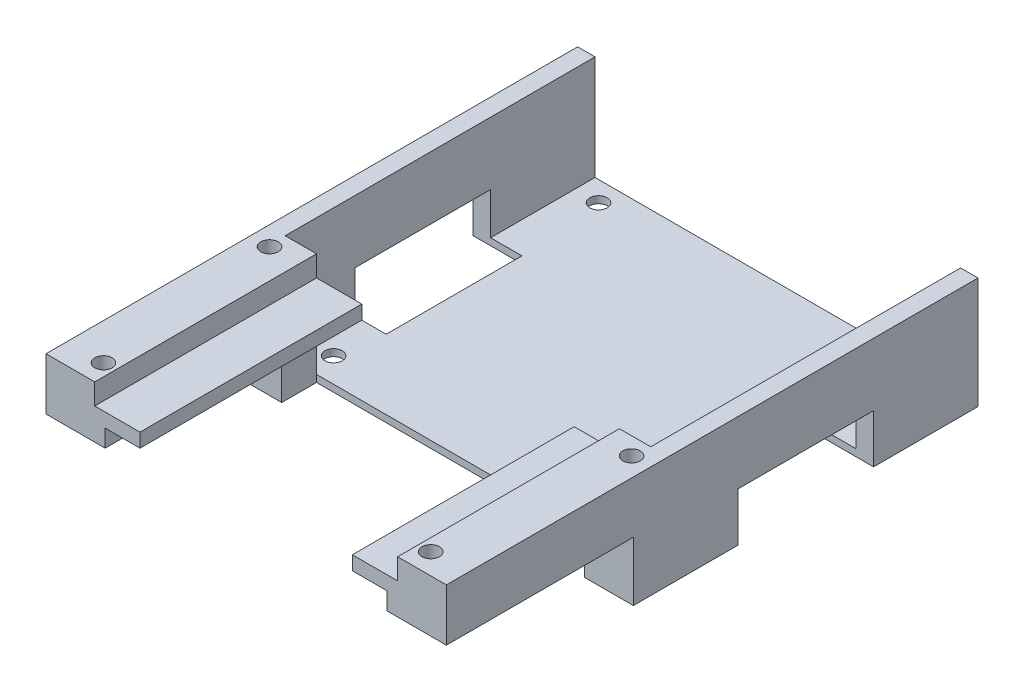
SolidWorks part; units mm, degrees
ref_plane "Front Plane" through (0, 0, 0) normal (0, 0, 1) x (1, 0, 0)
ref_plane "Top Plane" through (0, 0, 0) normal (0, 1, 0) x (1, 0, 0)
ref_plane "Right Plane" through (0, 0, 0) normal (1, 0, 0) x (0, 0, -1)
sketch "Sketch1" plane through (0, 0, 0) normal (0, 1, 0) x (1, 0, 0)
  line L0 (0, 0) -> (0, 76.35) construction
  line L1 (-28.75, 76.35) -> (28.75, 76.35)
  line L2 (28.75, 76.35) -> (28.75, 0)
  line L3 (28.75, 0) -> (21.75, 0)
  line L4 (21.75, 0) -> (21.75, 31.85)
  line L5 (21.75, 31.85) -> (-21.75, 31.85)
  line L6 (-21.75, 31.85) -> (-21.75, 0)
  line L7 (-21.75, 0) -> (-28.75, 0)
  line L8 (-28.75, 0) -> (-28.75, 76.35)
  line L9 (-26.25, 76.35) -> (-26.25, 31.85)
  line L14 (-26.25, 31.85) -> (-21.75, 31.85)
  line L15 (26.25, 76.35) -> (26.25, 31.85)
  line L16 (26.25, 31.85) -> (21.75, 31.85)
  line L17 (28.75, 74.35) -> (30.25, 74.35)
  line L18 (-28.75, 41.35) -> (-26.25, 41.35)
  line L19 (-28.75, 41.35) -> (-28.75, 53.35)
  line L20 (-28.75, 53.35) -> (-26.25, 53.35)
  line L21 (-26.25, 41.35) -> (-26.25, 53.35)
  line L22 (30.25, 68.35) -> (28.75, 68.35)
  line L23 (-30.25, 68.35) -> (-28.75, 68.35)
  line L24 (-28.75, 74.35) -> (-30.25, 74.35)
  arc A0 (30.25, 68.35) -> (30.25, 74.35) centre (30.25, 71.35) ccw
  arc A1 (-30.25, 68.35) -> (-30.25, 74.35) centre (-30.25, 71.35) cw
  point P10 (0, 76.35)
  point P16 (-27.5, 41.35)
  point P17 (-22.85, 73.45)
  point P18 (22.85, 73.45)
  point P23 (22.85, 35.4)
  point P24 (-22.85, 35.4)
  point P25 (23.5, 3)
  point P26 (26, 29.35)
  point P27 (-26, 29.35)
  point P28 (-23.5, 3)
  point P40 (30.25, 71.35)
  point P41 (-30.25, 71.35)
  dimension "D16" = 3
  dimension "D1" = 2.5
  dimension "D2" = 7
  dimension "D3" = 43.5
  dimension "D4" = 31.85
  dimension "D5" = 44.5
  dimension "D6" = 23
  dimension "D7" = 12
  dimension "D8" = 22.85
  dimension "D9" = 38.05
  dimension "D10" = 2.9
  dimension "D11" = 47
  dimension "D12" = 52
  dimension "D13" = 47
  dimension "D14" = 3
  dimension "D15" = 1.5
  dimension "D17" = 2
extrude "Boss-Extrude1" add sketch "Sketch1" along normal blind 1 contours L5 L0 L1 L9 L14 | L0 L5 L16 L15 L1 region at (-13.125, 0, -54.1) region at (13.125, 0, -54.1)
extrude "Boss-Extrude2" add sketch "Sketch1<3>" along normal blind 16 contours L18 L8 L7 L6 L14 L9 | L8 L20 L9 L1 | L15 L16 L4 L3 L2 L1 | L20 L8 L18 L9 region at (-27.5, 0, -64.85) region at (25.999, 0, -28.6329) region at (-27.5, 0, -47.35) region at (-25.4666, 0, -17.9154)
sketch "Sketch1<3>" plane through (0, 0, 0) normal (0, 1, 0) x (1, 0, 0) same geometry as "Sketch1"
hole_wizard "Ø2.5 (2.5) Diameter Hole1" positions "Sketch4" profile "Sketch5" hole size "Ø2.5" standard "ANSI Metric" end condition through all
sketch "Sketch4" plane through (0, 0, 0) normal (0, -1, 0) x (-1, 0, 0)
  point P0 (-22.85, 73.45)
  point P3 (22.85, 73.45)
  point P6 (26, 29.35)
  point P9 (22.85, 35.4)
  point P12 (-22.85, 35.4)
  point P15 (-26, 29.35)
  point P18 (-23.5, 3)
  point P21 (23.5, 3)
  point P24 (-30.25, 71.35)
  point P27 (30.25, 71.35)
sketch "Sketch5" plane through (22.85, 0, -73.45) normal (1, 0, 0) x (0, 0, -1)
  line L0 (0, 0) -> (0, 16)
  line L1 (0, 16) -> (1.25, 16)
  line L2 (1.25, 16) -> (1.25, 0)
  line L5 (1.25, 0) -> (0, 0)
  line L11 (0, -6.35) -> (0, 107.95) construction
  dimension "Thru Hole Dia." = 2.5
  dimension "Thru Hole Depth" = 16
sketch "Sketch6" plane through (0, 0, 0) normal (0, 0, 1) x (1, 0, 0)
  line L0 (-21.75, 16) -> (-21.75, 0) construction
  line L5 (0, -1.6497) -> (0, 21.9352) construction
  line L6 (-21.75, 11) -> (-15.25, 11)
  line L7 (-21.75, 11) -> (-21.75, 13)
  line L8 (-21.75, 13) -> (-15.25, 13)
  line L9 (-15.25, 11) -> (-15.25, 13)
  line L10 (-28.75, 16) -> (-28.75, 0) construction
  line L11 (-20.25, 11) -> (-21.75, 11)
  line L12 (-20.25, 11) -> (-20.25, 8.5)
  line L13 (-20.25, 8.5) -> (-21.75, 8.5)
  line L14 (-21.75, 11) -> (-21.75, 8.5)
  line L15 (-21.75, 0) -> (-28.75, 0)
  line L16 (-21.75, 0) -> (-21.75, 8.5)
  line L17 (-21.75, 8.5) -> (-28.75, 8.5)
  line L18 (-28.75, 0) -> (-28.75, 8.5)
  line L19 (28.75, 0) -> (28.75, 8.5)
  line L20 (21.75, 8.5) -> (28.75, 8.5)
  line L21 (21.75, 0) -> (21.75, 8.5)
  line L22 (21.75, 0) -> (28.75, 0)
  line L23 (21.75, 11) -> (21.75, 8.5)
  line L24 (20.25, 8.5) -> (21.75, 8.5)
  line L25 (20.25, 11) -> (20.25, 8.5)
  line L26 (20.25, 11) -> (21.75, 11)
  line L27 (15.25, 11) -> (15.25, 13)
  line L28 (21.75, 13) -> (15.25, 13)
  line L29 (21.75, 11) -> (21.75, 13)
  line L30 (21.75, 11) -> (15.25, 11)
  line L31 (-21.75, 16) -> (-28.75, 16) construction
  line M21 (21.75, 0) -> (28.75, 0)
  line M22 (28.75, 0) -> (28.75, 16)
  line M24 (21.75, 16) -> (21.75, 0)
  dimension "D1" = 6.5
  dimension "D2" = 3
  dimension "D3" = 2
  dimension "D4" = 2.5
  dimension "D5" = 1.5
extrude "Boss-Extrude3" add sketch "Sketch6" against normal up to surface (31.85 mm away) contours L30 L26 L28 L27 M24 | L26 L25 L24 M24 | L6 L9 L8 L7 | L6 L14 L13 L12 region at (-18.5, 12, 0) region at (-21, 9.75, 0) region at (21, 9.75, 0) region at (18.5, 12, 0) up to face at (0, 0.5, -31.85)
extrude "Cut-Extrude1" cut sketch "Sketch6<4>" against normal blind 26.85 contours L18 L15 L16 L17 | L20 M24 M21 M22 region at (-25.25, 4.25, 0) region at (25.25, 4.25, 0)
sketch "Sketch6<4>" plane through (0, 0, 0) normal (0, 0, 1) x (1, 0, 0) same geometry as "Sketch6"
sketch "Sketch8" plane through (0, 0, 0) normal (0, -1, 0) x (1, 0, 0)
  line L0 (0, 17.5937) -> (0, -89.2896) construction
  line L1 (-28.75, -61.35) -> (-21.75, -61.35)
  line L2 (-28.75, -61.35) -> (-28.75, -41.85)
  line L3 (-28.75, -41.85) -> (-21.75, -41.85)
  line L4 (-21.75, -61.35) -> (-21.75, -41.85)
  line L6 (-28.75, -76.35) -> (28.75, -76.35) construction
  line L8 (21.75, -61.35) -> (21.75, -41.85)
  line L9 (28.75, -41.85) -> (21.75, -41.85)
  line L10 (28.75, -61.35) -> (28.75, -41.85)
  line L11 (28.75, -61.35) -> (21.75, -61.35)
  line L12 (-28.75, -26.85) -> (-28.75, -76.35) construction
  dimension "D1" = 15
  dimension "D2" = 7
  dimension "D3" = 19.5
extrude "Cut-Extrude2" cut sketch "Sketch8" against normal blind 7
